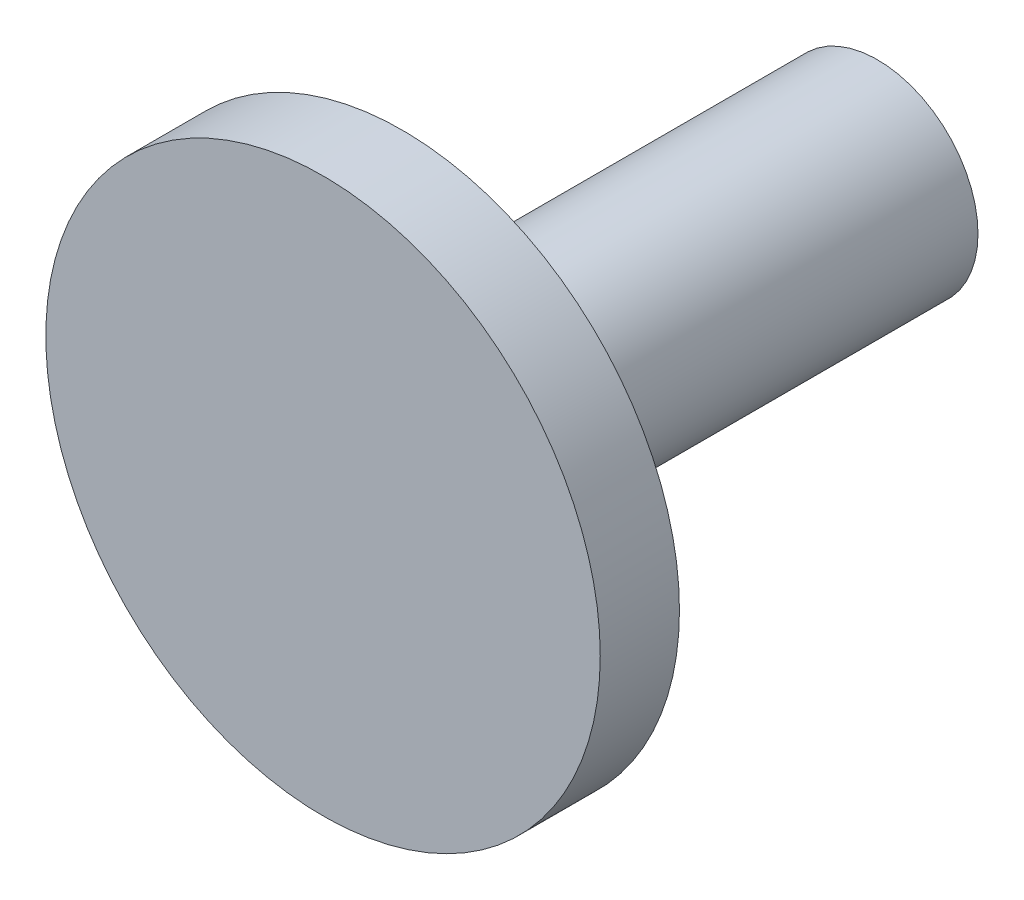
SolidWorks part; units mm, degrees
ref_plane "Front Plane" through (0, 0, 0) normal (0, 0, 1) x (1, 0, 0)
ref_plane "Top Plane" through (0, 0, 0) normal (0, 1, 0) x (1, 0, 0)
ref_plane "Right Plane" through (0, 0, 0) normal (1, 0, 0) x (0, 0, -1)
sketch "Sketch1" plane through (0, 0, 0) normal (0, 0, 1) x (1, 0, 0)
  circle A0 centre (0, 0) radius 17.5
  circle A1 centre (0, 0) radius 6.345
  dimension "D1" = 35
  dimension "D2" = 12.69
extrude "Boss-Extrude1" add sketch "Sketch1" along normal blind 5 contours A0
extrude "Boss-Extrude2" add sketch "Sketch1<3>" against normal blind 30 contours A1
sketch "Sketch1<3>" plane through (0, 0, 0) normal (0, 0, 1) x (1, 0, 0) same geometry as "Sketch1"
